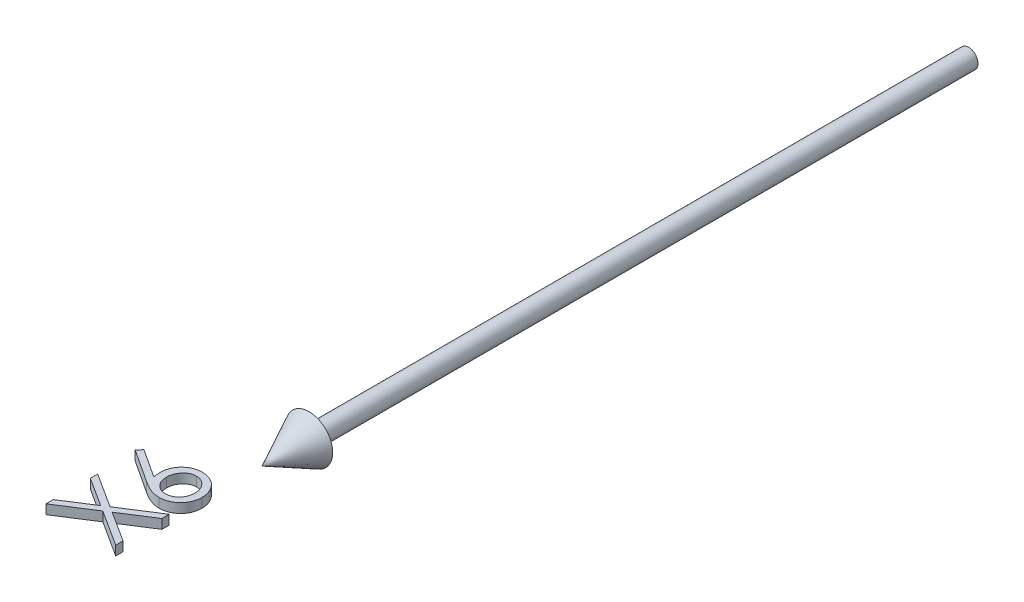
SolidWorks part; units mm, degrees
ref_plane "Front Plane" through (0, 0, 0) normal (0, 0, 1) x (1, 0, 0)
ref_plane "Top Plane" through (0, 0, 0) normal (0, 1, 0) x (1, 0, 0)
ref_plane "Right Plane" through (0, 0, 0) normal (1, 0, 0) x (0, 0, -1)
sketch "Sketch2" plane through (0, 0, 0) normal (0, 1, 0) x (1, 0, 0)
  line L0 (0, 41.95) -> (0, -114.4521) construction
  line L1 (-36.8894, 0) -> (41.4965, 0) construction
  line L2 (0, -150) -> (5, -140)
  line L3 (5, -140) -> (2, -140)
  line L4 (2, -140) -> (2, 0)
  line L5 (2, 0) -> (0, 0)
  line L6 (0, 0) -> (0, -150)
  dimension "D1" = 150
  dimension "D2" = 2
  dimension "D3" = 10
  dimension "D4" = 5
revolve "Revolve1" add sketch "Sketch2" angle 360 about L0
sketch "Sketch3" plane through (0, 0, 0) normal (0, 1, 0) x (1, 0, 0)
  line L0 (0, -157.5) -> (0, -205.8743) construction
  line L1 (-60.6951, 0) -> (44.3738, 0) construction
  text T0 "X6\r\n\r\n" font "Century Gothic" height 15
  dimension "D1" = 157.5
extrude "Boss-Extrude1" add sketch "Sketch3" against normal blind 1 and the other way blind 1 separate body
equation "\"D1@Sketch2\"=\"frame_arrow_length\""
equation "\"D2@Sketch2\"=\"frame_arrow_odA\"/2"
equation "\"D4@Sketch2\"=\"frame_arrow_head_od\""
equation "\"D3@Sketch2\"=\"frame_arrow_head_length\""
equation "\"frame_arrow_length\"=150"
equation "\"frame_arrow_head_length\"=10"
equation "\"frame_arrow_head_od\"=5"
equation "\"frame_arrow_odA\"=4"
equation "\"D1@Sketch3\"=\"frame_arrow_length\"*1.05"
